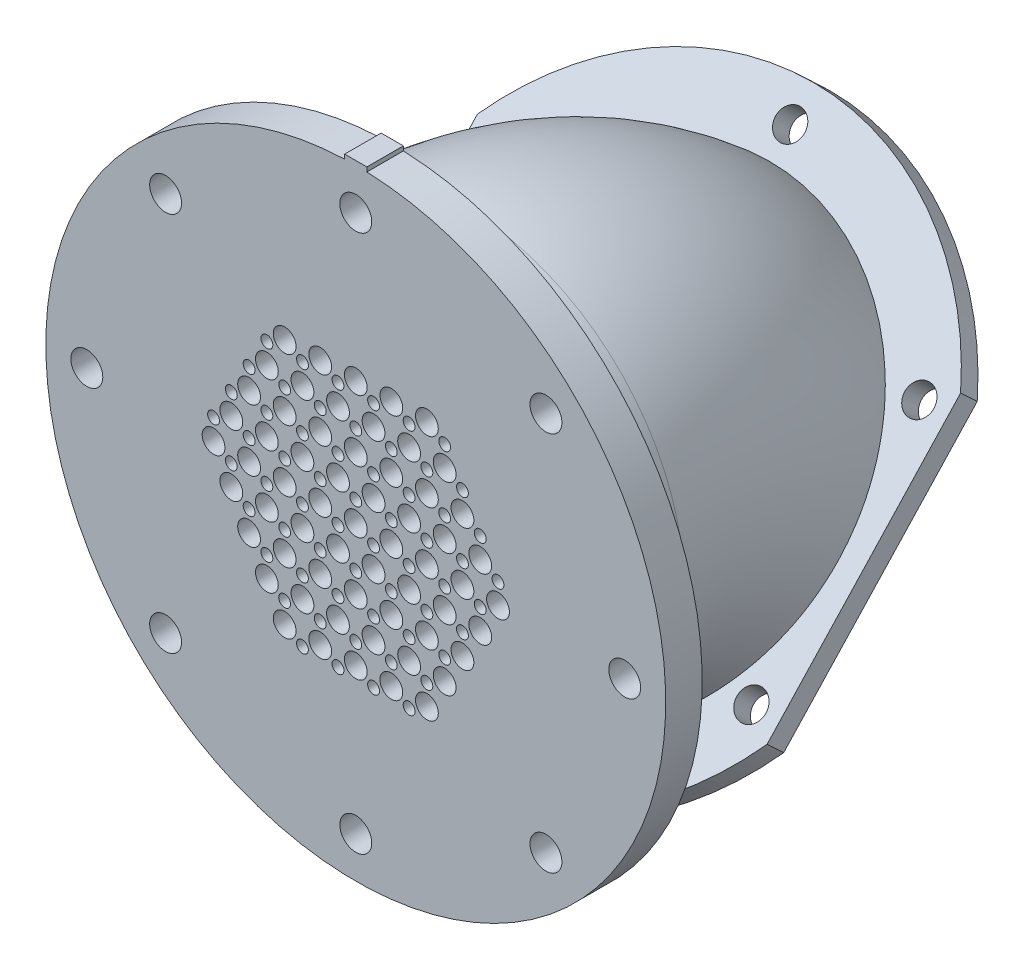
SolidWorks part; units mm, degrees
ref_plane "Спереди" through (0, 0, 0) normal (0, 0, 1) x (1, 0, 0)
ref_plane "Сверху" through (0, 0, 0) normal (0, 1, 0) x (1, 0, 0)
ref_plane "Справа" through (0, 0, 0) normal (1, 0, 0) x (0, 0, -1)
sketch "Sketch1" plane through (0, 0, 0) normal (0, 0, 1) x (1, 0, 0)
  line L0 (3.9, 6.755) -> (7.8, 0) construction
  line L2 (5.85, 10.1325) -> (11.7, 0) construction
  line L4 (7.8, 13.51) -> (15.6, 0) construction
  circle A61 centre (0, 0) radius 20
  circle A131 centre (0, 0) radius 1.25
  circle A484 centre (3.9, 0) radius 1.25
  circle A485 centre (7.8, 0) radius 1.25
  circle A486 centre (11.7, 0) radius 1.25
  circle A487 centre (15.6, 0) radius 1.25
  circle A488 centre (1.95, -3.3775) radius 1.25
  circle A489 centre (3.9, -6.755) radius 1.25
  circle A490 centre (5.85, -10.1325) radius 1.25
  circle A491 centre (7.8, -13.51) radius 1.25
  circle A492 centre (-1.95, -3.3775) radius 1.25
  circle A493 centre (-3.9, -6.755) radius 1.25
  circle A494 centre (-5.85, -10.1325) radius 1.25
  circle A495 centre (-7.8, -13.51) radius 1.25
  circle A496 centre (-3.9, 0) radius 1.25
  circle A497 centre (-7.8, 0) radius 1.25
  circle A498 centre (-11.7, 0) radius 1.25
  circle A499 centre (-15.6, 0) radius 1.25
  circle A500 centre (-1.95, 3.3775) radius 1.25
  circle A501 centre (-3.9, 6.755) radius 1.25
  circle A502 centre (-5.85, 10.1325) radius 1.25
  circle A503 centre (-7.8, 13.51) radius 1.25
  circle A504 centre (1.95, 3.3775) radius 1.25
  circle A505 centre (3.9, 6.755) radius 1.25
  circle A506 centre (5.85, 10.1325) radius 1.25
  circle A507 centre (7.8, 13.51) radius 1.25
  circle A508 centre (5.85, 3.3775) radius 1.25
  circle A509 centre (7.8, 6.755) radius 1.25
  circle A510 centre (9.75, 3.3775) radius 1.25
  circle A511 centre (11.7, 6.755) radius 1.25
  circle A512 centre (9.7491, 10.1341) radius 1.25
  circle A513 centre (13.6509, 3.3759) radius 1.25
  circle A514 centre (5.85, -3.3791) radius 1.25
  circle A515 centre (9.75, -3.3791) radius 1.25
  circle A516 centre (7.8, -6.7566) radius 1.25
  circle A517 centre (11.7, -6.7566) radius 1.25
  circle A518 centre (9.7491, -10.1356) radius 1.25
  circle A519 centre (13.6509, -3.3775) radius 1.25
  circle A520 centre (-0.0013, -6.7573) radius 1.25
  circle A521 centre (1.9487, -10.1348) radius 1.25
  circle A522 centre (-1.9513, -10.1348) radius 1.25
  circle A523 centre (-0.0013, -13.5123) radius 1.25
  circle A524 centre (-3.9032, -13.5123) radius 1.25
  circle A525 centre (3.9005, -13.5123) radius 1.25
  circle A526 centre (-5.8527, -3.3791) radius 1.25
  circle A527 centre (-7.8027, -6.7566) radius 1.25
  circle A528 centre (-9.7527, -3.3791) radius 1.25
  circle A529 centre (-11.7027, -6.7566) radius 1.25
  circle A530 centre (-13.6536, -3.3775) radius 1.25
  circle A531 centre (-9.7518, -10.1356) radius 1.25
  circle A532 centre (-5.8527, 3.3775) radius 1.25
  circle A533 centre (-9.7527, 3.3775) radius 1.25
  circle A534 centre (-7.8027, 6.755) radius 1.25
  circle A535 centre (-11.7027, 6.755) radius 1.25
  circle A536 centre (-9.7518, 10.1341) radius 1.25
  circle A537 centre (-13.6536, 3.3759) radius 1.25
  circle A538 centre (-0.0014, 6.7558) radius 1.25
  circle A539 centre (-1.9514, 10.1333) radius 1.25
  circle A540 centre (1.9486, 10.1333) radius 1.25
  circle A541 centre (-0.0014, 13.5108) radius 1.25
  circle A542 centre (3.9005, 13.5108) radius 1.25
  circle A543 centre (-3.9032, 13.5108) radius 1.25
  circle A544 centre (13.65, -1.1258) radius 2.2517 construction
  circle A545 centre (11.7009, -4.5044) radius 2.2522 construction
  circle A546 centre (9.75, -7.8834) radius 2.2522 construction
  circle A547 centre (7.7987, -11.2591) radius 2.2509 construction
  circle A548 centre (13.65, -1.1258) radius 0.65
  circle A549 centre (11.7009, -4.5044) radius 0.65
  circle A550 centre (9.75, -7.8834) radius 0.65
  circle A551 centre (7.7987, -11.2591) radius 0.65
  circle A552 centre (9.75, -1.1258) radius 0.65
  circle A553 centre (7.8009, -4.5044) radius 0.65
  circle A554 centre (5.85, -7.8834) radius 0.65
  circle A555 centre (3.8987, -11.2591) radius 0.65
  circle A556 centre (5.85, -1.1258) radius 0.65
  circle A557 centre (3.9009, -4.5044) radius 0.65
  circle A558 centre (1.95, -7.8834) radius 0.65
  circle A559 centre (-0.0013, -11.2591) radius 0.65
  circle A560 centre (1.95, -1.1258) radius 0.65
  circle A561 centre (0.0009, -4.5044) radius 0.65
  circle A562 centre (-1.95, -7.8834) radius 0.65
  circle A563 centre (-3.9013, -11.2591) radius 0.65
  circle A564 centre (-1.95, -1.1258) radius 0.65
  circle A565 centre (-3.8991, -4.5044) radius 0.65
  circle A566 centre (-5.85, -7.8834) radius 0.65
  circle A567 centre (-7.8013, -11.2591) radius 0.65
  circle A568 centre (-5.85, -1.1258) radius 0.65
  circle A569 centre (-7.7991, -4.5044) radius 0.65
  circle A570 centre (-9.75, -7.8834) radius 0.65
  circle A572 centre (-9.75, -1.1258) radius 0.65
  circle A573 centre (-11.6991, -4.5044) radius 0.65
  circle A576 centre (-13.65, -1.1258) radius 0.65
  circle A580 centre (-15.5991, -4.5044) radius 0.65 [skipped]
  circle A581 centre (-13.65, -7.8834) radius 0.65 [skipped]
  circle A582 centre (-17.55, -7.8834) radius 0.65 [skipped]
  circle A583 centre (-19.5013, -11.2591) radius 0.65 [skipped]
  circle A584 centre (-15.6013, -11.2591) radius 0.65 [skipped]
  circle A585 centre (-11.7013, -11.2591) radius 0.65 [skipped]
  circle A587 centre (0, 2.2517) radius 2.2517 construction
  circle A588 centre (0, 2.2517) radius 0.65
  circle A589 centre (3.9, 2.2517) radius 0.65
  circle A590 centre (7.8, 2.2517) radius 0.65
  circle A591 centre (11.7, 2.2517) radius 0.65
  circle A592 centre (15.6, 2.2517) radius 0.65
  circle A593 centre (1.9491, 5.6297) radius 2.2522 construction
  circle A594 centre (1.9491, 5.6297) radius 0.65
  circle A595 centre (5.8491, 5.6297) radius 0.65
  circle A596 centre (9.7491, 5.6297) radius 0.65
  circle A597 centre (13.6491, 5.6297) radius 0.65
  circle A598 centre (3.8991, 9.0072) radius 2.2522 construction
  circle A599 centre (3.8991, 9.0072) radius 0.65
  circle A600 centre (7.7991, 9.0072) radius 0.65
  circle A601 centre (11.6991, 9.0072) radius 0.65
  circle A602 centre (5.85, 12.3842) radius 2.2517 construction
  circle A603 centre (5.85, 12.3842) radius 0.65
  circle A604 centre (9.75, 12.3842) radius 0.65
  circle A605 centre (5.85, -14.6358) radius 0.65
  circle A606 centre (1.9509, -14.6353) radius 0.65
  circle A607 centre (-1.9491, -14.6353) radius 0.65
  circle A608 centre (-5.85, -14.6358) radius 0.65
  circle A609 centre (-15.6, 2.2517) radius 0.65
  circle A610 centre (-13.65, 5.6281) radius 0.65
  circle A611 centre (-11.7, 9.0056) radius 0.65
  circle A612 centre (-9.75, 12.3842) radius 0.65
  circle A613 centre (-5.85, 12.3842) radius 0.65
  circle A614 centre (-1.95, 12.3842) radius 0.65
  circle A615 centre (1.95, 12.3842) radius 0.65
  circle A616 centre (-7.8, 9.0056) radius 0.65
  circle A617 centre (-9.75, 5.6281) radius 0.65
  circle A618 centre (-11.7, 2.2517) radius 0.65
  circle A619 centre (-3.9, 9.0056) radius 0.65
  circle A620 centre (-5.85, 5.6281) radius 0.65
  circle A621 centre (-7.8, 2.2517) radius 0.65
  circle A622 centre (0, 9.0056) radius 0.65
  circle A623 centre (-1.95, 5.6281) radius 0.65
  circle A624 centre (-3.9, 2.2517) radius 0.65
  point P51 (0, 0)
  point P125 (-0.0013, -0.0008)
  point P231 (0, 0)
  dimension "D1" = 5
  dimension "D3" = 6
  dimension "D5" = 8
  dimension "D7" = 4
  dimension "D2" = 6
  dimension "D6" = 5
  dimension "D8" = 3
  dimension "D9" = 2
  dimension "D4" = 1.3
  dimension "D10" = 3
sketch "Sketch2" plane through (0, 0, 0) normal (1, 0, 0) x (0, 0, -1)
  line L0 (0, 0) -> (12, 0)
  line L1 (39.4234, -27.4234) -> (39.4234, -34.4234)
  arc A0 (12, 0) -> (39.4234, -27.4234) centre (12, -27.4234) cw
  dimension "D1" = 27.4234
sketch "Sketch4" plane through (0, 0, 0) normal (1, 0, 0) x (0, 0, -1)
  line L1 (-31.2382, 44.0572) -> (87.6543, 44.0572)
  line L2 (-31.2382, 44.0572) -> (-31.2382, -52.5019)
  line L3 (-31.2382, -52.5019) -> (87.6543, -52.5019)
  line L4 (87.6543, 44.0572) -> (87.6543, -52.5019)
sweep "Sweep1" add profiles "Sketch1" path "Sketch2"
sketch "Sketch5" plane through (0, 0, 0) normal (0, 0, 1) x (1, 0, 0)
  circle A0 centre (0, 0) radius 23.5 construction
  circle A1 centre (0, 0) radius 34
  circle A2 centre (0, 0) radius 17.1737
extrude "Boss-Extrude1" add sketch "Sketch5" against normal blind 4
fillet "Fillet1" radius 2 1 edges at (20, 0, -4)
sketch "Sketch8" plane through (0, 0, 0) normal (0, 0, 1) x (1, 0, 0)
  line L0 (0, 0) -> (-19.915, 0)
  line L1 (0, 0) -> (-20.8597, 20.8597) construction
  circle A0 centre (0, 0) radius 29.5 construction
  circle A1 centre (-20.8597, 20.8597) radius 1.75
  circle A2 centre (20.8597, 20.8597) radius 1.75
  circle A3 centre (20.8597, -20.8597) radius 1.75
  circle A4 centre (-20.8597, -20.8597) radius 1.75
  point P15 (0, 0)
  dimension "D1" = 4
extrude "Cut-Extrude3" cut sketch "Sketch8" against normal blind 5 contours A2 | A1 | A4 | A3 region at (-20.8597, 20.8597, 0) region at (20.8597, 20.8597, 0) region at (20.8597, -20.8597, 0) region at (-20.8597, -20.8597, 0)
sketch "Sketch9" plane through (0, 0, 0) normal (1, 0, 0) x (0, 0, -1)
  line L0 (17.2491, -22.1743) -> (45.1688, 7.7454) construction
  line L1 (17.2491, -22.1743) -> (55.0922, 18.3797)
  line L2 (55.0922, 18.3797) -> (79.742, -4.6224)
  line L3 (79.742, -4.6224) -> (81.4428, -51.3917)
  line L4 (81.4428, -51.3917) -> (9.2513, -51.3917)
  line L5 (9.2513, -51.3917) -> (8.5286, -31.5195)
  line L7 (17.2491, -22.1743) -> (8.5286, -31.5195)
  arc A0 (19.4234, -27.4234) -> (12, -20) centre (12, -27.4234) ccw construction
ref_plane "Plane1" through (0, 0, -10) normal (0, 0, 1) x (1, 0, 0)
sketch "Sketch10" plane through (0, 0, -10) normal (0, 0, 1) x (1, 0, 0)
  line L1 (-46.7536, 40.8154) -> (60.8519, 40.8154)
  line L2 (-46.7536, 40.8154) -> (-46.7536, -39.2382)
  line L3 (-46.7536, -39.2382) -> (60.8519, -39.2382)
  line L4 (60.8519, 40.8154) -> (60.8519, -39.2382)
extrude "Cut-Extrude4" cut sketch "Sketch10" against normal blind 50
sketch "Sketch18" plane through (0, 0, 0) normal (0, 0, 1) x (1, 0, 0)
  circle A0 centre (0, 0) radius 19
  circle A1 centre (0, 0) radius 24
sweep "Sweep2" add profiles "Sketch18" path "Sketch2<2>"
sketch "Sketch2<2>" plane through (0, 0, 0) normal (1, 0, 0) x (0, 0, -1) same geometry as "Sketch2"
extrude "Cut-Extrude6" cut sketch "Sketch9" against normal through all both and the other way through all
sketch "Sketch21" plane through (0, -18.9253, -20.2809) normal (0, -0.6822, -0.7311) x (-1, 0, 0)
  circle A0 centre (0.0014, 15.3483) radius 20.75
  dimension "D1" = 41.5
extrude "Cut-Extrude7" cut sketch "Sketch21" against normal blind 4.55
sketch "Sketch23" plane through (0, -18.9253, -20.2809) normal (0, -0.6822, -0.7311) x (-1, 0, 0)
  circle A0 centre (0.0014, 15.7866) radius 22.7295
  circle A1 centre (0.0014, 15.7866) radius 30.7295
  ellipse E1 centre (0.0014, 16.7005) end of major axis (1.2514, 16.7005) minor radius 0.9139 construction
  dimension "D1" = 8
extrude "Boss-Extrude2" add sketch "Sketch23" against normal blind 2.5 contours A1 | A0
sketch "Sketch24" plane through (0, -17.2196, -18.4531) normal (0, 0.6822, 0.7311) x (1, 0, 0)
  circle A0 centre (0, 42.7878) radius 1.6
  circle A1 centre (23.382, 29.2867) radius 1.6
  circle A2 centre (23.3807, 2.2867) radius 1.6
  circle A3 centre (-0.0014, 15.7878) radius 27 construction
  circle A6 centre (-0.0014, 15.7878) radius 27 construction
  circle A8 centre (-0.0014, 15.7878) radius 27 construction
  circle A9 centre (-0.0027, -11.2122) radius 1.6
  circle A10 centre (-23.3847, 2.289) radius 1.6
  circle A11 centre (-23.3834, 29.289) radius 1.6
  point P9 (-0.0014, 15.7878)
  point P20 (-0.0014, 15.7878)
  dimension "D1" = 3
  dimension "D2" = 6
extrude "Cut-Extrude8" cut sketch "Sketch24" against normal blind 2.5
sketch "Sketch27" plane through (0, 0, 0) normal (0, 0, 1) x (1, 0, 0)
  circle A0 centre (0, 0) radius 29.5 construction
  circle A1 centre (0, 29.5) radius 1.75
  circle A2 centre (29.5, 0) radius 1.75
  circle A3 centre (0, -29.5) radius 1.75
  circle A4 centre (-29.5, 0) radius 1.75
  point P15 (0, 0)
extrude "Cut-Extrude9" cut sketch "Sketch27" against normal blind 5
sketch "Sketch28" plane through (0, 0, 0) normal (0, 0, 1) x (1, 0, 0)
  line L1 (-1.218, 34.4616) -> (1.218, 34.4616)
  line L2 (-1.218, 34.4616) -> (-1.218, 33.5384)
  line L3 (-1.218, 33.5384) -> (1.218, 33.5384)
  line L4 (1.218, 34.4616) -> (1.218, 33.5384)
  line L5 (-1.218, 34.4616) -> (1.218, 33.5384) construction
  line L6 (-1.218, 33.5384) -> (1.218, 34.4616) construction
  circle A0 centre (0, 0) radius 34 construction
  point P0 (0, 34)
extrude "Boss-Extrude3" add sketch "Sketch28" against normal blind 4
sketch "Sketch29" plane through (0, -18.9253, -20.2809) normal (0, -0.6822, -0.7311) x (-1, 0, 0)
  line L1 (-26.5, -61.8154) -> (26.5, -61.8154)
  line L2 (-26.5, -61.8154) -> (-26.5, 61.8154)
  line L3 (-26.5, 61.8154) -> (26.5, 61.8154)
  line L4 (26.5, -61.8154) -> (26.5, 61.8154)
  line L5 (-26.5, -61.8154) -> (26.5, 61.8154) construction
  line L6 (-26.5, 61.8154) -> (26.5, -61.8154) construction
  line L7 (-57.3906, 74.7913) -> (57.3906, 74.7913)
  line L8 (-57.3906, 74.7913) -> (-57.3906, -74.7913)
  line L9 (-57.3906, -74.7913) -> (57.3906, -74.7913)
  line L10 (57.3906, 74.7913) -> (57.3906, -74.7913)
  line L11 (-57.3906, 74.7913) -> (57.3906, -74.7913) construction
  line L12 (-57.3906, -74.7913) -> (57.3906, 74.7913) construction
  point P0 (0, 0)
  point P6 (0, 0)
extrude "Cut-Extrude10" cut sketch "Sketch29" against normal blind 3
